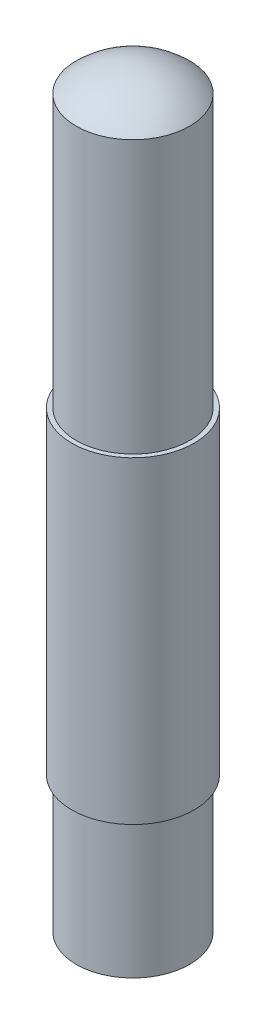
SolidWorks part; units mm, degrees
ref_plane "Ön Düzlem" through (0, 0, 0) normal (0, 0, 1) x (1, 0, 0)
ref_plane "Üst Düzlem" through (0, 0, 0) normal (0, 1, 0) x (1, 0, 0)
ref_plane "Sağ Düzlem" through (0, 0, 0) normal (1, 0, 0) x (0, 0, -1)
sketch "Çizim1" plane through (0, 0, 0) normal (0, 0, 1) x (1, 0, 0)
  line L0 (0, 0) -> (-12.5, 0)
  line L1 (-12.5, 0) -> (-12.5, 30)
  line L2 (-12.5, 30) -> (-13.5, 30)
  line L3 (-13.5, 30) -> (-13.5, 100)
  line L4 (-13.5, 100) -> (-12.5, 100)
  line L5 (-12.5, 100) -> (-12.5, 160)
  line L6 (-12.5, 160) -> (0, 160)
  line L7 (0, 160) -> (0, 0) construction
  line L8 (0, 0) -> (0, 160)
  dimension "D1" = 160
  dimension "D2" = 13.5
  dimension "D3" = 25
  dimension "D4" = 25
  dimension "D5" = 60
  dimension "D6" = 30
revolve "Döndür2" add sketch "Çizim1" angle 360 about L7
cosmetic thread "Kozmetik Diş Açma1" parameters "D2"=23.38
cosmetic thread "Kozmetik Diş Açma2" parameters "D2"=20.704
dome "Kubbe1" faces to dome 1 distance 5 reverse direction no elliptical dome no face at (0, 160, 12.5) parameters "D1"=5
